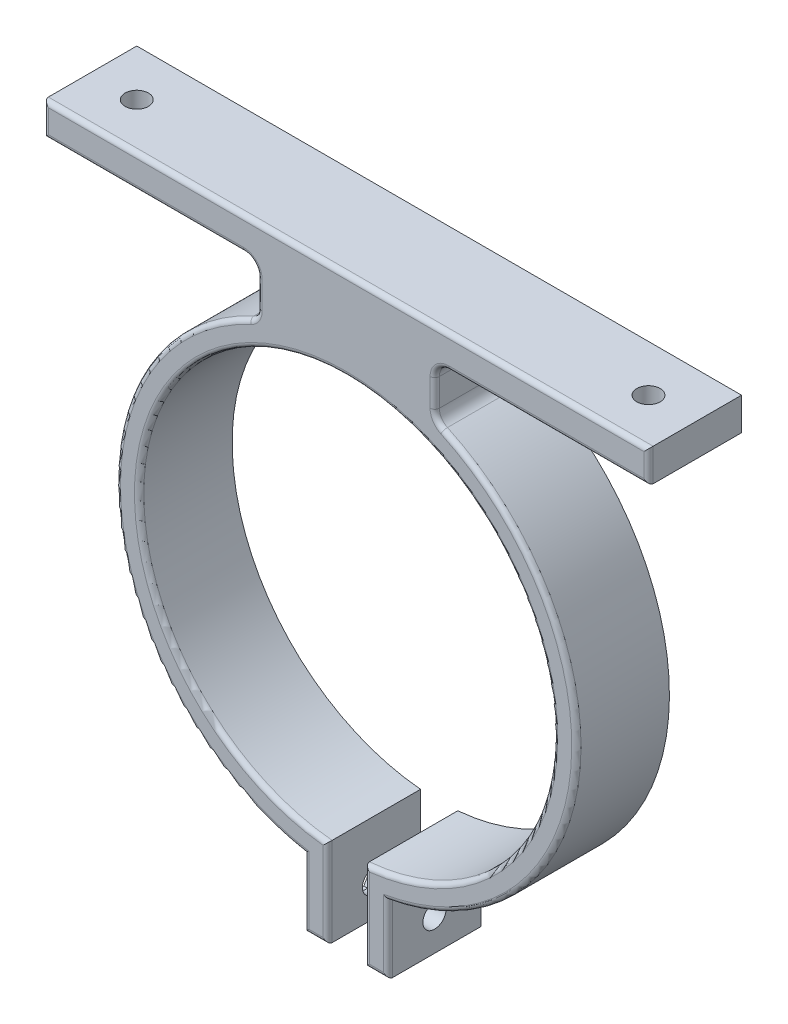
SolidWorks part; units mm, degrees
ref_plane "Front Plane" through (0, 0, 0) normal (0, 0, 1) x (1, 0, 0)
ref_plane "Top Plane" through (0, 0, 0) normal (0, 1, 0) x (1, 0, 0)
ref_plane "Right Plane" through (0, 0, 0) normal (1, 0, 0) x (0, 0, -1)
sketch "Sketch1" plane through (0, 0, 0) normal (0, 0, 1) x (1, 0, 0)
  line L0 (0, -240.3264) -> (0, 11775.9931) construction
  line L1 (4, -44.3199) -> (4, -63.3699)
  line L2 (-4, -44.3199) -> (-4, -63.3699)
  line L3 (9, -48.6749) -> (9, -63.3699)
  line L4 (-9, -48.6749) -> (-9, -63.3699)
  line L5 (9, -63.3699) -> (4, -63.3699)
  line L6 (4, -63.3699) -> (3.7317, -63.226)
  line L7 (-4, -63.3699) -> (-9, -63.3699)
  line L8 (-9, -63.3699) -> (-9.1837, -63.1122)
  line L9 (-65, 56.55) -> (-19.05, 56.55)
  line L10 (-65, 63.55) -> (65, 63.55)
  line L11 (-65, 63.55) -> (-65, 56.55)
  line L12 (19.05, 56.55) -> (65, 56.55)
  line L13 (65, 63.55) -> (65, 56.55)
  line L14 (-1000, 44.5) -> (49000, 44.5) construction
  line L15 (-19.05, 56.55) -> (-19.05, 45.6875)
  line L16 (19.05, 56.55) -> (19.05, 45.6875)
  line L17 (0, 0) -> (4, -44.3199) construction
  line L18 (4, -44.3199) -> (3.9202, -44.2806) construction
  line L19 (0, 0) -> (-4, -44.3199) construction
  arc A0 (4, -44.3199) -> (-4, -44.3199) centre (0, 0) ccw
  arc A1 (9, -48.6749) -> (19.05, 45.6875) centre (0, 0) ccw
  arc A2 (-19.05, 45.6875) -> (-9, -48.6749) centre (0, 0) ccw
  arc A4 (9, -48.6749) -> (-9, -48.6749) centre (0, 0) ccw construction
  point P24 (0, 44.5)
  dimension "D1" = 4
  dimension "D5" = 44.5
  dimension "D2" = 4
  dimension "D3" = 19.05
  dimension "D4" = 19.05
  dimension "D7" = 65
  dimension "D8" = 65
  dimension "D9" = 19.05
  dimension "D10" = 19.05
  dimension "D11" = 7
  dimension "D12" = 10.314
  dimension "D6" = 5
extrude "Boss-Extrude1" add sketch "Sketch1" along normal blind 20 contours L12 A2 L4 L7 L2 A0 L1 L5 L3 A1 L13 L10 L11 region at (0, 46.3168, 0)
fillet "Fillet1" radius 3 4 edges at (19.05, 45.6875, 10) (19.05, 56.55, 10) (-19.05, 45.6875, 10) (-19.05, 56.55, 10)
ref_plane "Plane1" through (0, 56.55, 0) normal (0, -1, 0) x (-1, 0, 0)
sketch "Sketch2" plane through (0, 56.55, 0) normal (0, -1, 0) x (-1, 0, 0)
  line L0 (-22.05, -20) -> (-65, -20) construction
  line L1 (65, -20) -> (65, 0) construction
  line L5 (-65, -20) -> (-65, 0) construction
  line L6 (-22.05, -20) -> (-65, -20) construction
  circle A0 centre (55, -10) radius 2.5
  circle A1 centre (-55, -10) radius 2.5
  dimension "D1" = 10
  dimension "D3" = 10
  dimension "D2" = 10
  dimension "D4" = 10
extrude "Cut-Extrude1" cut sketch "Sketch2" against normal through all
ref_plane "Plane2" through (-9, 0, 0) normal (-1, 0, 0) x (0, 0, 1)
sketch "Sketch3" plane through (-9, 0, 0) normal (-1, 0, 0) x (0, 0, 1)
  line L0 (20, -48.6749) -> (20, -63.3699) construction
  line L2 (20, -63.3699) -> (0, -63.3699) construction
  line L4 (15.6003, -56.3699) -> (12.8001, -51.5199)
  line L5 (12.8001, -51.5199) -> (7.1999, -51.5199)
  line L6 (7.1999, -51.5199) -> (4.3997, -56.3699)
  line L7 (4.3997, -56.3699) -> (7.1999, -61.2199)
  line L8 (7.1999, -61.2199) -> (12.8001, -61.2199)
  line L9 (12.8001, -61.2199) -> (15.6003, -56.3699)
  circle A0 centre (10, -56.3699) radius 2.5
  circle A1 centre (10, -56.3699) radius 4.85 construction
  dimension "D1" = 10
  dimension "D3" = 9.7
  dimension "D2" = 7
extrude "Cut-Extrude2" cut sketch "Sketch3" against normal through all contours A0 region at (-9, -56.3699, 10)
extrude "Cut-Extrude3" cut sketch "Sketch3<4>" against normal blind 3.175
sketch "Sketch3<4>" plane through (-9, 0, 0) normal (-1, 0, 0) x (0, 0, 1) same geometry as "Sketch3"
fillet "Fillet2" radius 1 20 edges at (-65, 60.05, 20) (0, 63.55, 20) (65, 60.05, 20) (43.525, 56.55, 20) (19.9287, 55.6713, 20) (19.05, 50.5975, 20) (19.5222, 46.0295, 20) (49.1119, -6.1864, 20) (9, -56.0224, 20) (6.5, -63.3699, 20) (4, -53.8449, 20) (0, 44.5, 20) (-4, -53.8449, 20) (-6.5, -63.3699, 20) (-9, -56.0224, 20) (-49.1119, -6.1864, 20) (-19.5222, 46.0295, 20) (-19.05, 50.5975, 20) (-19.9287, 55.6713, 20) (-43.525, 56.55, 20)
